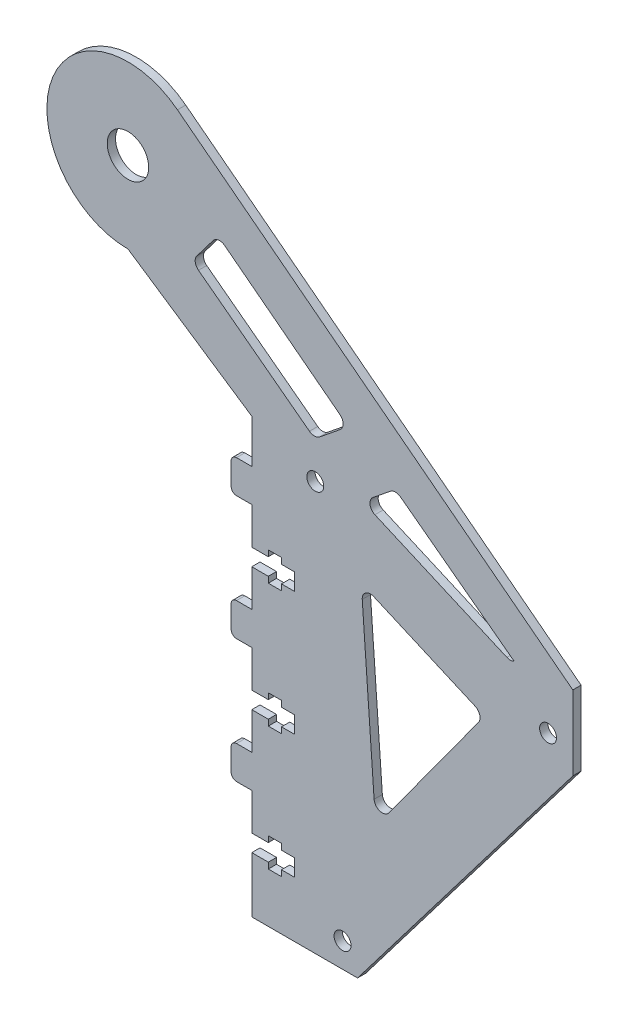
SolidWorks part; units mm, degrees
ref_plane "前视基准面" through (0, 0, 0) normal (0, 0, 1) x (1, 0, 0)
ref_plane "上视基准面" through (0, 0, 0) normal (0, 1, 0) x (1, 0, 0)
ref_plane "右视基准面" through (0, 0, 0) normal (1, 0, 0) x (0, 0, -1)
sketch "草图1" plane through (0, 0, 0) normal (0, 0, 1) x (1, 0, 0)
  line L4 (298.5456, -83.8944) -> (298.5456, -92.8418)
  line L15 (298.5456, -96.9418) -> (302.5456, -96.9418)
  line L16 (302.5456, -96.9418) -> (302.5456, -98.3918)
  line L17 (302.5456, -98.3918) -> (305.7456, -98.3918)
  line L18 (305.7456, -98.3918) -> (305.7456, -96.9418)
  line L19 (305.7456, -96.9418) -> (308.9456, -96.9418)
  line L20 (308.9456, -96.9418) -> (308.9456, -92.8418)
  line L21 (308.9456, -92.8418) -> (305.7456, -92.8418)
  line L22 (305.7456, -92.8418) -> (305.7456, -91.3918)
  line L23 (305.7456, -91.3918) -> (302.5456, -91.3918)
  line L24 (302.5456, -91.3918) -> (302.5456, -92.8418)
  line L25 (302.5456, -92.8418) -> (298.5456, -92.8418)
  line L27 (298.5456, -94.8944) -> (302.5431, -94.8944) construction
  line L28 (298.5456, -109.8944) -> (303.5456, -109.8944) construction
  line L29 (303.5456, -113.8944) -> (293.5456, -113.8944) construction
  line L30 (303.5456, -113.8944) -> (303.5456, -105.8944) construction
  line L31 (303.5456, -105.8944) -> (293.5456, -105.8944) construction
  line L32 (293.5456, -113.8944) -> (293.5456, -105.8944)
  line L33 (303.5456, -113.8944) -> (293.5456, -105.8944) construction
  line L34 (303.5456, -105.8944) -> (293.5456, -113.8944) construction
  line L35 (302.5456, -126.947) -> (298.5456, -126.947)
  line L36 (298.5456, -122.847) -> (302.5456, -122.847)
  line L37 (302.5456, -128.397) -> (302.5456, -126.947)
  line L38 (305.7456, -128.397) -> (302.5456, -128.397)
  line L39 (305.7456, -126.947) -> (305.7456, -128.397)
  line L40 (308.9456, -126.947) -> (305.7456, -126.947)
  line L41 (308.9456, -122.847) -> (308.9456, -126.947)
  line L42 (305.7456, -122.847) -> (308.9456, -122.847)
  line L43 (305.7456, -121.397) -> (305.7456, -122.847)
  line L44 (302.5456, -121.397) -> (305.7456, -121.397)
  line L45 (302.5456, -122.847) -> (302.5456, -121.397)
  line L46 (293.5456, -75.8944) -> (293.5456, -83.8944)
  line L47 (302.5456, -62.8418) -> (298.5456, -62.8418)
  line L48 (298.5456, -66.9418) -> (302.5456, -66.9418)
  line L49 (302.5456, -66.9418) -> (302.5456, -68.3918)
  line L50 (302.5456, -68.3918) -> (305.7456, -68.3918)
  line L51 (305.7456, -68.3918) -> (305.7456, -66.9418)
  line L52 (305.7456, -66.9418) -> (308.9456, -66.9418)
  line L53 (308.9456, -66.9418) -> (308.9456, -62.8418)
  line L54 (308.9456, -62.8418) -> (305.7456, -62.8418)
  line L55 (305.7456, -62.8418) -> (305.7456, -61.3918)
  line L56 (305.7456, -61.3918) -> (302.5456, -61.3918)
  line L57 (302.5456, -61.3918) -> (302.5456, -62.8418)
  line L58 (293.5456, -83.8944) -> (298.5456, -83.8944)
  line L59 (293.5456, -75.8944) -> (298.5456, -75.8944)
  line L60 (298.5456, -75.8944) -> (298.5456, -66.9418)
  line L63 (298.5456, -105.8944) -> (293.5456, -105.8944)
  line L64 (293.5456, -113.8944) -> (298.5456, -113.8944)
  line L65 (298.5456, -113.8944) -> (298.5456, -122.847)
  line L66 (308.9456, -64.8918) -> (305.2429, -64.8918) construction
  line L67 (293.5456, -45.8892) -> (298.5456, -45.8892)
  line L68 (293.5456, -53.8892) -> (293.5456, -45.8892)
  line L69 (293.5456, -53.8892) -> (298.5456, -53.8892)
  line L70 (298.5456, -53.8892) -> (298.5456, -62.8418)
  line L78 (298.5456, -126.947) -> (298.5456, -140.447)
  line L79 (298.5456, -140.447) -> (324.1889, -140.447)
  line L84 (376.3586, -71.947) -> (324.1889, -140.447)
  line L85 (298.5456, -45.8892) -> (298.5456, -35.347)
  line L89 (320.5456, -134.447) -> (313.937, -41.347) construction
  line L90 (313.937, -41.347) -> (370.3586, -65.947) construction
  line L91 (370.3586, -65.947) -> (320.5456, -134.447) construction
  line L92 (354.9473, -70.1368) -> (328.5796, -106.3961)
  line L93 (328.5796, -106.3961) -> (325.0814, -57.1152)
  line L94 (325.0814, -57.1152) -> (354.9473, -70.1368)
  line L101 (298.5456, -96.9418) -> (298.5456, -105.8944)
  line L107 (376.3586, -71.947) -> (376.3586, -53.8892)
  line L111 (268.537, 4.3962) -> (370.3586, -65.947) construction
  line L114 (298.5456, -35.347) -> (268.537, -15.2538)
  line L115 (376.3586, -53.8892) -> (280.5318, 19.9605)
  line L116 (313.937, -41.347) -> (274.2196, -11.3292) construction
  line L119 (313.937, -41.347) -> (333.1895, -25.708) construction
  line L120 (333.1895, -25.708) -> (367.5855, -51.569) construction
  line L121 (367.5855, -51.569) -> (370.3586, -65.947) construction
  line L122 (333.3323, -33.3221) -> (362.1319, -54.9754)
  line L123 (362.1319, -54.9754) -> (362.3087, -55.8917)
  line L124 (325.3729, -39.7876) -> (362.3087, -55.8917)
  line L125 (325.3729, -39.7876) -> (333.3323, -33.3221)
  line L126 (274.2196, -11.3292) -> (289.0415, 8.2822) construction
  line L127 (289.0415, 8.2822) -> (333.1895, -25.708) construction
  line L128 (290.3675, -1.573) -> (321.9061, -25.8551)
  line L129 (313.7813, -32.455) -> (321.9061, -25.8551)
  line L130 (313.7813, -32.455) -> (284.0247, -9.9654)
  line L131 (284.0247, -9.9654) -> (290.3675, -1.573)
  circle A11 centre (268.537, 4.3962) radius 5.0225
  circle A14 centre (268.537, 4.3962) radius 19.65 construction
  circle A24 centre (320.5456, -134.447) radius 2.05
  circle A25 centre (370.3586, -65.947) radius 2.05
  circle A26 centre (313.937, -41.347) radius 2.05
  arc A52 (268.537, -15.2538) -> (280.5318, 19.9605) centre (268.537, 4.3962) cw
  point P20 (300.5444, -94.8944)
  point P30 (298.5456, -109.8944)
  dimension "D3" = 4.1
  dimension "D4" = 10.045
  dimension "D5" = 3.2
  dimension "D6" = 6
  dimension "D15" = 22
  dimension "D17" = 6
  dimension "D7" = 7
  dimension "D8" = 4
  dimension "D9" = 2.0526
  dimension "D10" = 15
  dimension "D11" = 8
  dimension "D12" = 10
  dimension "D14" = 13.5
  dimension "D16" = 6
  dimension "D18" = 6
  dimension "D30" = 7
  dimension "D21" = 10
extrude "凸台-拉伸1" add sketch "草图1" along normal blind 2
sketch "草图2" plane through (298.5456, 0, 0) normal (-1, 0, 0) x (0, 0, 1)
  line L0 (1, -66.9418) -> (1, -62.8418)
  line L1 (2, -66.9418) -> (0, -66.9418) construction
  line L2 (2, -62.8418) -> (0, -62.8418) construction
  circle A0 centre (1, -64.8918) radius 2.05
fillet "圆角1" radius 2 10 edges at (325.0814, -57.1152, 1) (328.5796, -106.3961, 1) (354.9473, -70.1368, 1) (362.3087, -55.8917, 1) (333.3323, -33.3221, 1) (325.3729, -39.7876, 1) (321.9061, -25.8551, 1) (313.7813, -32.455, 1) (290.3675, -1.573, 1) (284.0247, -9.9654, 1)
fillet "圆角2" radius 1.3 6 edges at (293.5456, -45.8892, 1) (293.5456, -53.8892, 1) (293.5456, -83.8944, 1) (293.5456, -75.8944, 1) (293.5456, -113.8944, 1) (293.5456, -105.8944, 1)
